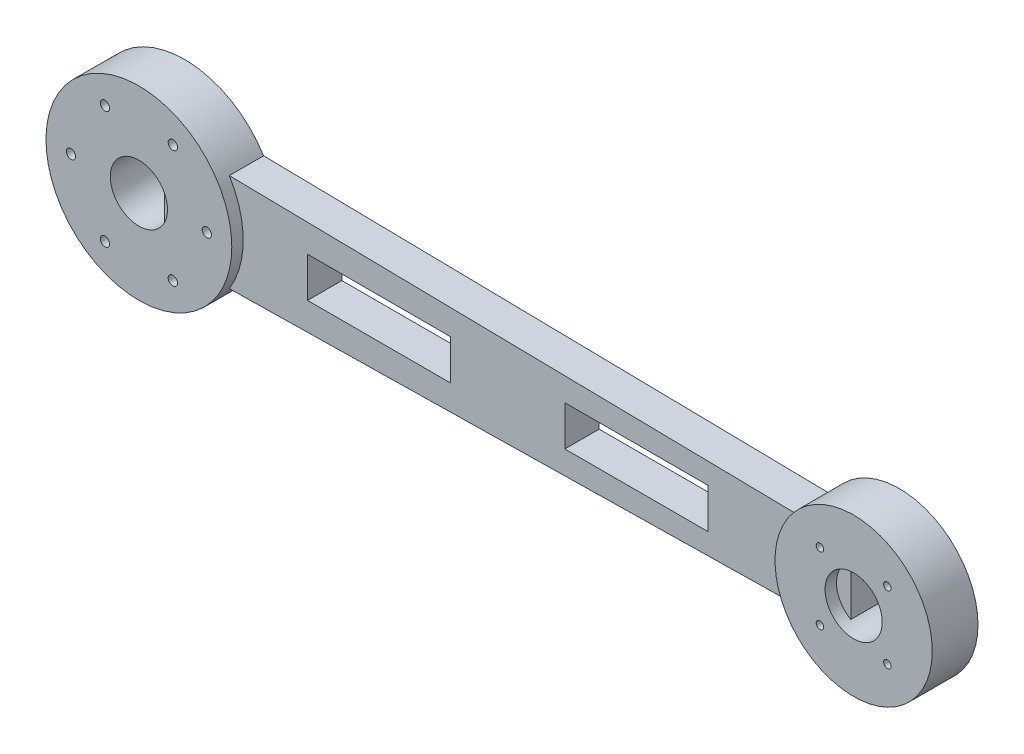
SolidWorks part; units mm, degrees
ref_plane "Front Plane" through (0, 0, 0) normal (0, 0, 1) x (1, 0, 0)
ref_plane "Top Plane" through (0, 0, 0) normal (0, 1, 0) x (1, 0, 0)
ref_plane "Right Plane" through (0, 0, 0) normal (1, 0, 0) x (0, 0, -1)
sketch "Sketch1" plane through (0, 0, 0) normal (0, 0, 1) x (1, 0, 0)
  circle A0 centre (0, 0) radius 65
  circle A1 centre (0, 0) radius 20
  circle A2 centre (47.5, 0) radius 3.25
  circle A3 centre (23.75, 41.1362) radius 3.25
  circle A4 centre (-23.75, 41.1362) radius 3.25
  circle A5 centre (-47.5, 0) radius 3.25
  circle A6 centre (-23.75, -41.1362) radius 3.25
  circle A7 centre (23.75, -41.1362) radius 3.25
extrude "Boss-Extrude1" add sketch "Sketch1" along normal blind 32
sketch "Sketch2" plane through (0, 0, 0) normal (0, 0, 1) x (1, 0, 0)
  circle A0 centre (500, 0) radius 55
  circle A1 centre (500, 0) radius 20
  circle A2 centre (476.43, -23.57) radius 2.6
  circle A3 centre (476.43, 23.57) radius 2.6
  circle A4 centre (523.57, -23.57) radius 2.6
  circle A5 centre (523.57, 23.57) radius 2.6
extrude "Boss-Extrude2" add sketch "Sketch2" along normal blind 32
sketch "Sketch3" plane through (0, 0, 0) normal (0, 0, 1) x (1, 0, 0)
  line L0 (10, -35) -> (10, 35)
  line L1 (10, 35) -> (490, 27)
  line L2 (490, 27) -> (490, -27)
  line L3 (490, -27) -> (10, -35)
  line L5 (110, -14) -> (210, -14)
  line L6 (110, -14) -> (110, 14)
  line L7 (110, 14) -> (210, 14)
  line L8 (210, -14) -> (210, 14)
  line L9 (110, -14) -> (210, 14) construction
  line L10 (110, 14) -> (210, -14) construction
  line L11 (290, -14) -> (390, -14)
  line L12 (290, -14) -> (290, 14)
  line L13 (290, 14) -> (390, 14)
  line L14 (390, -14) -> (390, 14)
  line L15 (290, -14) -> (390, 14) construction
  line L16 (290, 14) -> (390, -14) construction
  point P4 (160, 0)
  point P9 (340, 0)
extrude "Boss-Extrude3" add sketch "Sketch3" along normal blind 24
ref_axis "Axis1" through (0, 0, -1.6) along (0, 0, 1)
ref_plane "Elbow Plane" through (500, 0, 0) normal (1, 0, 0) x (0, 0, -1)
ref_axis "Axis2" through (500, 0, -1.6) along (0, 0, 1)
sketch3d "3DSketch1"
  point P0 (500, 0, 32)
